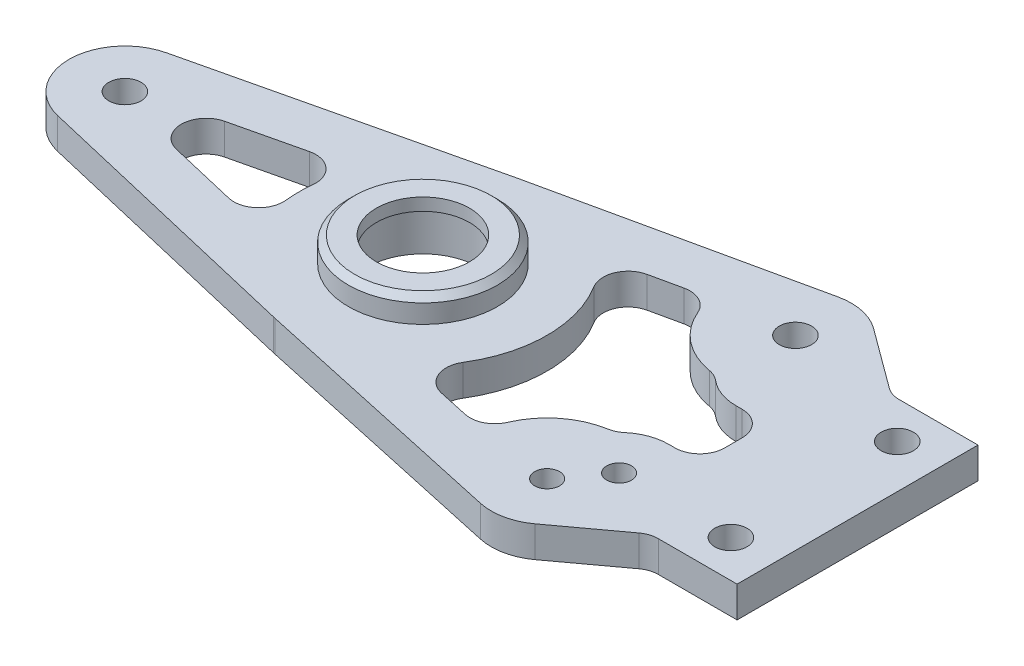
SolidWorks part; units mm, degrees
ref_plane "Front Plane" through (0, 0, 0) normal (0, 0, 1) x (1, 0, 0)
ref_plane "Top Plane" through (0, 0, 0) normal (0, 1, 0) x (1, 0, 0)
ref_plane "Right Plane" through (0, 0, 0) normal (1, 0, 0) x (0, 0, -1)
sketch "Sketch1" plane through (0, 0, 0) normal (0, 1, 0) x (1, 0, 0)
  line L0 (35, 9.7) -> (35, -9.7)
  line L1 (35, 9.7) -> (28.6566, 9.7)
  line L2 (35, -9.7) -> (28.6566, -9.7)
  line L3 (7.5892, 0) -> (-24.2432, 0) construction
  line L4 (22.5919, 5) -> (-33.5892, 5) construction
  line L5 (22.5919, -5) -> (-33.5892, -5) construction
  line L6 (28, 29.9214) -> (28, -27.3936) construction
  line L7 (-21, 30.6326) -> (-21, -25.3784) construction
  line L8 (31, 30.8205) -> (31, -25.1937) construction
  line L9 (0, 34.0703) -> (0, -31.8389) construction
  line L10 (-25.0312, 4.3802) -> (-2.2917, 9.7339)
  line L11 (-2.1347, 9.7695) -> (19.0394, 14.3963)
  line L12 (-25.0312, -4.3802) -> (-2.2917, -9.7339)
  line L13 (-2.1347, -9.7695) -> (19.0394, -14.3963)
  line L14 (22.6672, 13.6244) -> (27.4712, 10.0892)
  line L15 (22.6672, -13.6244) -> (27.4712, -10.0892)
  line L16 (9.7721, 8.2769) -> (12.2163, 8.811)
  line L17 (-17.9129, -1.9468) -> (-12.3876, -3.2476)
  line L18 (-17.9129, 1.9468) -> (-12.3876, 3.2476)
  line L20 (25, 0.7) -> (25, -0.7)
  line L21 (22.5, 2.7) -> (23, 2.7)
  line L22 (22.5, -2.7) -> (23, -2.7)
  line L25 (9.7721, -8.2769) -> (12.2163, -8.811)
  circle A0 centre (31.5, 6.7) radius 1.3
  circle A1 centre (31.5, -6.7) radius 1.3
  circle A2 centre (0, 0) radius 12 construction
  circle A3 centre (0, 0) radius 13.5 construction
  circle A4 centre (20, 10) radius 5 construction
  circle A5 centre (20, -10) radius 5 construction
  circle A6 centre (20, 10) radius 6.5 construction
  circle A7 centre (20, -10) radius 6.5 construction
  circle A8 centre (20, 10) radius 1.3
  circle A9 centre (20, -10) radius 1
  circle A10 centre (0, 0) radius 4.5
  circle A11 centre (-24, 0) radius 1.3
  circle A12 centre (22.5, -6.7) radius 1
  arc A13 (22.6672, 13.6244) -> (19.0394, 14.3963) centre (20, 10) ccw
  arc A14 (19.0394, -14.3963) -> (22.6672, -13.6244) centre (20, -10) ccw
  arc A15 (-2.1347, 9.7695) -> (-2.2917, 9.7339) centre (0, 0) ccw
  arc A16 (-25.0312, 4.3802) -> (-25.0312, -4.3802) centre (-24, 0) ccw
  arc A17 (28.6566, -9.7) -> (27.4712, -10.0892) centre (28.6566, -11.7) ccw
  arc A18 (28.6566, 9.7) -> (27.4712, 10.0892) centre (28.6566, 11.7) cw
  arc A19 (-2.2917, -9.7339) -> (-2.1347, -9.7695) centre (0, 0) ccw
  arc A20 (8.4992, 5.2692) -> (8.4992, -5.2691) centre (0, 0) cw
  arc A21 (14.4824, 7.6428) -> (18.9688, 4.0893) centre (20, 10) ccw
  arc A22 (18.9688, -4.0893) -> (14.4824, -7.6428) centre (20, -10) ccw
  arc A23 (-17.9129, -1.9468) -> (-17.9129, 1.9468) centre (-17.4545, 0) cw
  arc A24 (-9.9411, -1.084) -> (-9.9411, 1.084) centre (0, 0) cw
  arc A25 (22.5, -2.7) -> (19.9167, -3.646) centre (22.5, -6.7) ccw
  arc A27 (14.4824, -7.6428) -> (12.2163, -8.811) centre (12.6432, -6.8571) cw
  arc A28 (19.9167, 3.646) -> (22.5, 2.7) centre (22.5, 6.7) ccw
  arc A29 (18.9688, -4.0893) -> (19.9167, -3.646) centre (18.6251, -2.119) ccw
  arc A30 (23, -2.7) -> (25, -0.7) centre (23, -0.7) ccw
  arc A31 (23, 2.7) -> (25, 0.7) centre (23, 0.7) cw
  arc A32 (18.9688, 4.0893) -> (19.9167, 3.646) centre (18.6251, 2.119) cw
  arc A33 (12.2163, 8.811) -> (14.4824, 7.6428) centre (12.6432, 6.8571) cw
  arc A34 (9.7721, 8.2769) -> (8.4992, 5.2692) centre (10.199, 6.323) ccw
  arc A35 (8.4992, -5.2691) -> (9.7721, -8.2769) centre (10.199, -6.323) ccw
  arc A36 (-9.9411, -1.084) -> (-12.3876, -3.2476) centre (-11.9293, -1.3008) cw
  arc A37 (-9.9411, 1.084) -> (-12.3876, 3.2476) centre (-11.9293, 1.3008) ccw
  point P27 (0, 0)
  point P28 (20, 10)
  point P29 (20, -10)
  point P45 (28, -9.7)
  point P58 (28, 9.7)
  dimension "D1" = 2.6
  dimension "D2" = 2.6
  dimension "D8" = 7
  dimension "D11" = 5
  dimension "D14" = 20
  dimension "D15" = 20
  dimension "D16" = 2.6
  dimension "D17" = 2.6
  dimension "D18" = 2
  dimension "D19" = 9
  dimension "D23" = 2
  dimension "D25" = 9
  dimension "D26" = 9
  dimension "D27" = 20
  dimension "D28" = 9
  dimension "D29" = 2
  dimension "D30" = 10
  dimension "D33" = 6
  dimension "D42" = 6
  dimension "D34" = 4
  dimension "D36" = 2
  dimension "D37" = 10
  dimension "D44" = 3
  dimension "D31" = 4
  dimension "D43" = 4
  dimension "D47" = 2
  dimension "D3" = 13.4
  dimension "D4" = 3.5
  dimension "D5" = 3.5
  dimension "D6" = 3
  dimension "D7" = 3
  dimension "D9" = 7
  dimension "D10" = 9.7
  dimension "D12" = 5
  dimension "D13" = 28
  dimension "D20" = 24
  dimension "D21" = 31
  dimension "D22" = 21
  dimension "D24" = 9
  dimension "D32" = 3
  dimension "D35" = 4
  dimension "D38" = 4
  dimension "D39" = 4
  dimension "D40" = 20
  dimension "D41" = 10
  dimension "D45" = 3
  dimension "D46" = 9
extrude "Boss-Extrude1" add sketch "Sketch1" along normal blind 2.5
cosmetic thread "Cosmetic Thread1" parameters "D2"=2.5
cosmetic thread "Cosmetic Thread3" parameters "D2"=2.5
ref_axis "Axis1" through (0, 11.4389, 0) along (0, -1, 0)
sketch "Sketch3" plane through (0, 2.5, 0) normal (0, 1, 0) x (1, 0, 0)
  circle A0 centre (0, 0) radius 3.75
  circle A1 centre (0, 0) radius 6
  dimension "D1" = 7.5
  dimension "D2" = 12
extrude "Boss-Extrude2" add sketch "Sketch3" along normal blind 2
sketch "Sketch4" plane through (0, 2.5, 0) normal (0, -1, 0) x (1, 0, 0)
  circle A0 centre (0, 0) radius 3.75
  circle A1 centre (0, 0) radius 4.5
extrude "Cut-Extrude1" cut sketch "Sketch4" against normal blind 1
chamfer "Chamfer1" distance 0.5 angle 45 1 edges at (0, 4.5, 6)
sketch "Sketch6" plane through (0, 0, 0) normal (0, -1, 0) x (1, 0, 0)
  circle A0 centre (20, 10) radius 3
  circle A1 centre (20, -10) radius 3
extrude "Cut-Extrude2" cut sketch "Sketch6" against normal blind 0.5
